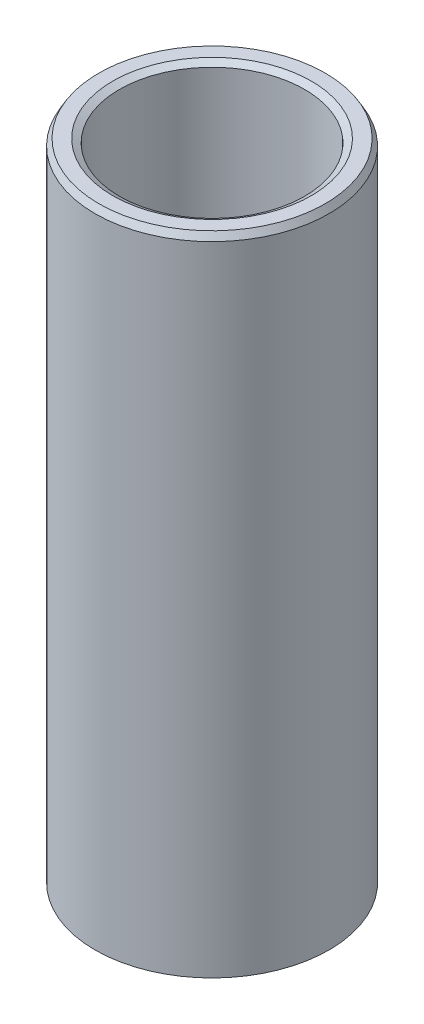
SolidWorks part; units mm, degrees
ref_plane "Front Plane" through (0, 0, 0) normal (0, 0, 1) x (1, 0, 0)
ref_plane "Top Plane" through (0, 0, 0) normal (0, 1, 0) x (1, 0, 0)
ref_plane "Right Plane" through (0, 0, 0) normal (1, 0, 0) x (0, 0, -1)
sketch "Sketch1" plane through (0, 0, 0) normal (0, 1, 0) x (1, 0, 0)
  circle A0 centre (0, 0) radius 50
  dimension "SLEEVE_OD" = 100
extrude "Boss-Extrude1" add sketch "Sketch1" along normal blind 276.9087
sketch "Sketch2" plane through (0, 0, 0) normal (0, 1, 0) x (1, 0, 0)
  circle A0 centre (0, 0) radius 39.5646
  dimension "BORE_D" = 79.1292
extrude "Cut-Extrude1" cut sketch "Sketch2" along normal through all
chamfer "Chamfer1" distance 2.8527 angle 30 4 edges at (0, 276.9087, 39.5646) (0, 0, 39.5646) (0, 0, 50) (0, 276.9087, 50) first distance on face at (0, 276.9087, 39.5646) first distance on face at (0, 0, 39.5646) first distance on face at (0, 276.9087, 50)
